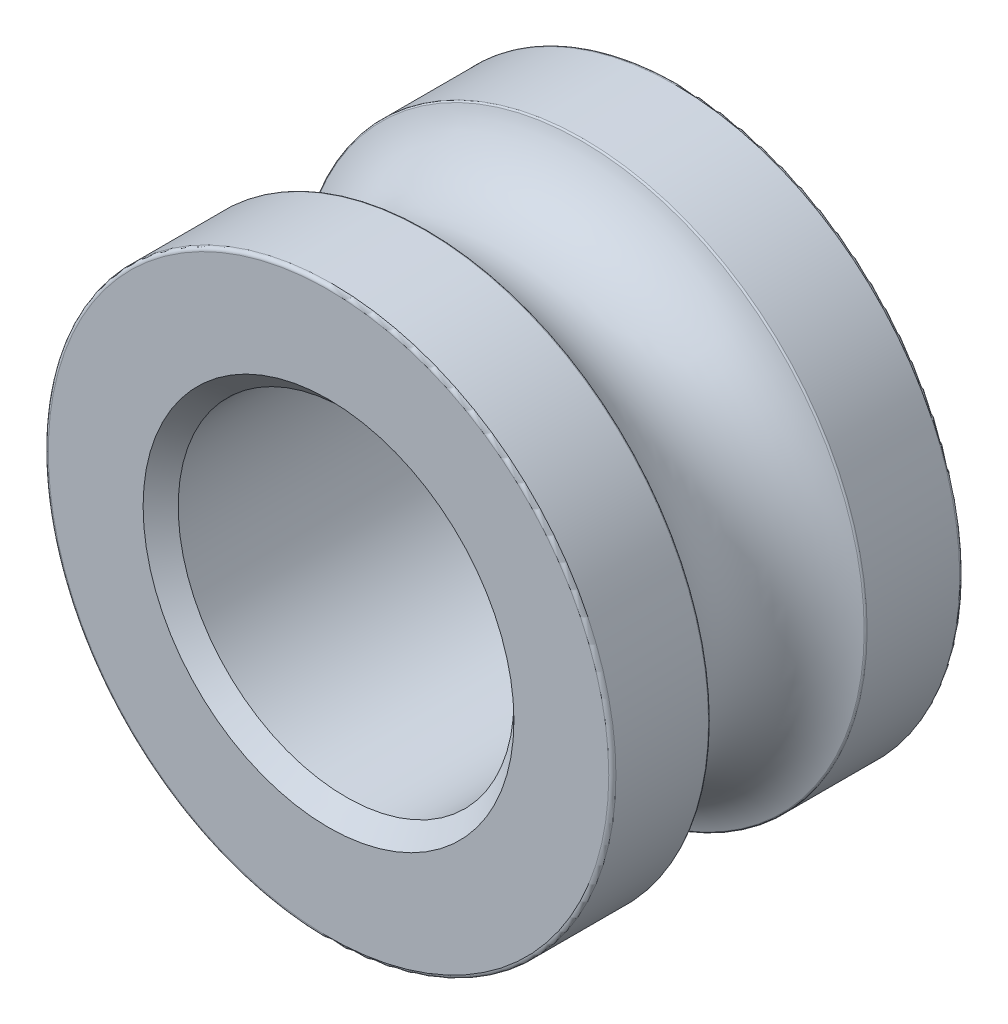
SolidWorks part; units mm, degrees
material "Stainless Steel (ferritic)"
ref_plane "Front Plane" through (0, 0, 0) normal (0, 0, 1) x (1, 0, 0)
ref_plane "Top Plane" through (0, 0, 0) normal (0, 1, 0) x (1, 0, 0)
ref_plane "Right Plane" through (0, 0, 0) normal (1, 0, 0) x (0, 0, -1)
ref_axis "Central Axis" through (0, 0, -2.7381) along (0, 0, 1)
sketch "Layout Sketch" plane through (0, 0, 0) normal (1, 0, 0) x (0, 0, -1)
  line L0 (-2.4892, 0) -> (2.4892, 0) construction
  line L1 (0, 6.35) -> (0, -6.35) construction
  line L2 (2.2403, 6.35) -> (-2.2403, 6.35)
  line L3 (-2.2403, 6.35) -> (-2.4892, 6.1011)
  line L4 (-2.4892, 6.1011) -> (-2.4892, 4.705)
  line L5 (-2.4892, 4.705) -> (-1.1063, 4.705)
  line L6 (2.4892, 4.705) -> (1.1063, 4.705)
  line L7 (2.4892, 6.1011) -> (2.4892, 4.705)
  line L8 (2.2403, 6.35) -> (2.4892, 6.1011)
  line L9 (0, 6.35) -> (0, 4.3656) construction
  line L10 (0, 4.3656) -> (0, 2.3813) construction
  arc A0 (-1.1063, 4.705) -> (1.1063, 4.705) centre (0, 4.3656) cw
  point P14 (0, 2.3813)
  dimension "Width" = 4.9784
  dimension "OD" = 12.7
  dimension "D1" = 45
  dimension "D2" = 0.2489
  dimension "D3" = 2.2126
  dimension "D4" = 0.3394
  dimension "D5" = 2.3813
sketch "Inner Bearing Race Profile" plane through (0, 0, 0) normal (1, 0, 0) x (0, 0, -1)
  line L2 (-2.4892, 6.1011) -> (-2.4892, 4.705) construction
  line L3 (-2.4892, 4.3656) -> (2.4892, 4.3656) construction
  line L5 (-2.4892, 6.35) -> (2.4892, 6.35) construction
  line L6 (2.2403, 6.35) -> (2.4892, 6.1011) construction
  line L8 (2.4892, 4.705) -> (1.1063, 4.705) construction
  line L10 (-2.4892, 4.705) -> (-1.1063, 4.705) construction
  line L12 (2.4892, 6.1011) -> (2.4892, 4.705) construction
  line L14 (2.2403, 6.35) -> (-2.2403, 6.35) construction
  line L17 (-2.2403, 6.35) -> (-2.4892, 6.1011) construction
  line L18 (-2.2403, 6.35) -> (-2.4892, 6.1011) construction
  line L19 (-2.4892, 6.1011) -> (-2.4892, 4.705) construction
  line L20 (-2.4892, 4.705) -> (-1.1063, 4.705) construction
  line L21 (2.4892, 4.705) -> (1.1063, 4.705) construction
  line L22 (2.4892, 6.1011) -> (2.4892, 4.705) construction
  line L23 (2.2403, 6.35) -> (2.4892, 6.1011) construction
  line L25 (2.2403, 6.35) -> (-2.2403, 6.35)
  line L26 (-2.2403, 6.35) -> (-2.4892, 6.1011)
  line L27 (-2.4892, 6.1011) -> (-2.4892, 4.705)
  line L28 (-2.4892, 4.705) -> (-1.1063, 4.705)
  line L29 (1.1063, 4.705) -> (2.4892, 4.705)
  line L30 (2.4892, 4.705) -> (2.4892, 6.1011)
  line L31 (2.4892, 6.1011) -> (2.2403, 6.35)
  line L32 (2.2403, 6.35) -> (-2.2403, 6.35) construction
  line L33 (-2.2403, 6.35) -> (-2.4892, 6.1011) construction
  line L34 (-2.4892, 6.1011) -> (-2.4892, 4.705) construction
  line L35 (-2.4892, 4.705) -> (-1.1063, 4.705) construction
  line L36 (1.1063, 4.705) -> (2.4892, 4.705) construction
  line L37 (2.4892, 4.705) -> (2.4892, 6.1011) construction
  line L38 (2.4892, 6.1011) -> (2.2403, 6.35) construction
  line L45 (2.2403, 2.3813) -> (2.4892, 2.6302)
  line L46 (2.4892, 2.6302) -> (2.4892, 3.9754)
  line L47 (2.4384, 4.0262) -> (1.1249, 4.0262)
  line L48 (-2.4384, 4.0262) -> (-1.1249, 4.0262)
  line L49 (-2.4892, 2.6302) -> (-2.4892, 3.9754)
  line L50 (-2.2403, 2.3813) -> (-2.4892, 2.6302)
  line L53 (2.2403, 2.3813) -> (-2.2403, 2.3813)
  arc A0 (1.1249, 4.0262) -> (1.1008, 4.0086) centre (1.1249, 4.0008) ccw
  arc A1 (1.1063, 4.705) -> (-1.1063, 4.705) centre (0, 4.3656) ccw construction
  arc A2 (1.1063, 4.705) -> (-1.1063, 4.705) centre (0, 4.3656) ccw construction
  arc A3 (1.1063, 4.705) -> (-1.1063, 4.705) centre (0, 4.3656) ccw
  arc A4 (1.1063, 4.705) -> (-1.1063, 4.705) centre (0, 4.3656) ccw construction
  arc A5 (-1.1008, 4.0086) -> (-1.1249, 4.0262) centre (-1.1249, 4.0008) ccw
  arc A6 (1.1008, 4.0086) -> (-1.1008, 4.0086) centre (0, 4.3656) cw
  arc A7 (2.4892, 3.9754) -> (2.4384, 4.0262) centre (2.4384, 3.9754) ccw
  arc A8 (-2.4892, 3.9754) -> (-2.4384, 4.0262) centre (-2.4384, 3.9754) cw
  point P6 (0, 6.35)
  point P17 (1.1063, 4.0262)
  point P20 (-1.1063, 4.0262)
  point P23 (2.4892, 4.0262)
  point P27 (-2.4892, 4.0262)
  dimension "D2" = 0.0254
  dimension "D3" = 0.0508
  dimension "D1" = 0
revolve "Inner Bearing Race" add sketch "Inner Bearing Race Profile" angle 360 about L0
sketch "Bearing Assembly Layout Curve Profile" plane through (0, 0, 0) normal (0, 0, 1) x (1, 0, 0)
  circle A0 centre (0, 0) radius 4.3656
curve "Bearing Assembly Layout Curve"
sketch "Inner Race Bearing Gear Profile" plane through (0, 0, 0) normal (0, 0, 1) x (1, 0, 0)
  circle A0 centre (0, 0) radius 3.2084
  circle A1 centre (0, 0) radius 3.2084
curve "Inner Race Bearing Gear Curve"
equation "\"D2@Layout Sketch\" = \"Width@Layout Sketch\" * .05"
equation "\"D3@Layout Sketch\" = \"Width@Layout Sketch\" / 2.25"
equation "\"D4@Layout Sketch\" =  (  (  ( \"OD@Layout Sketch\" - \"Width@Layout Sketch\" )  / 2 )  / 3.25 )  / 3.5"
